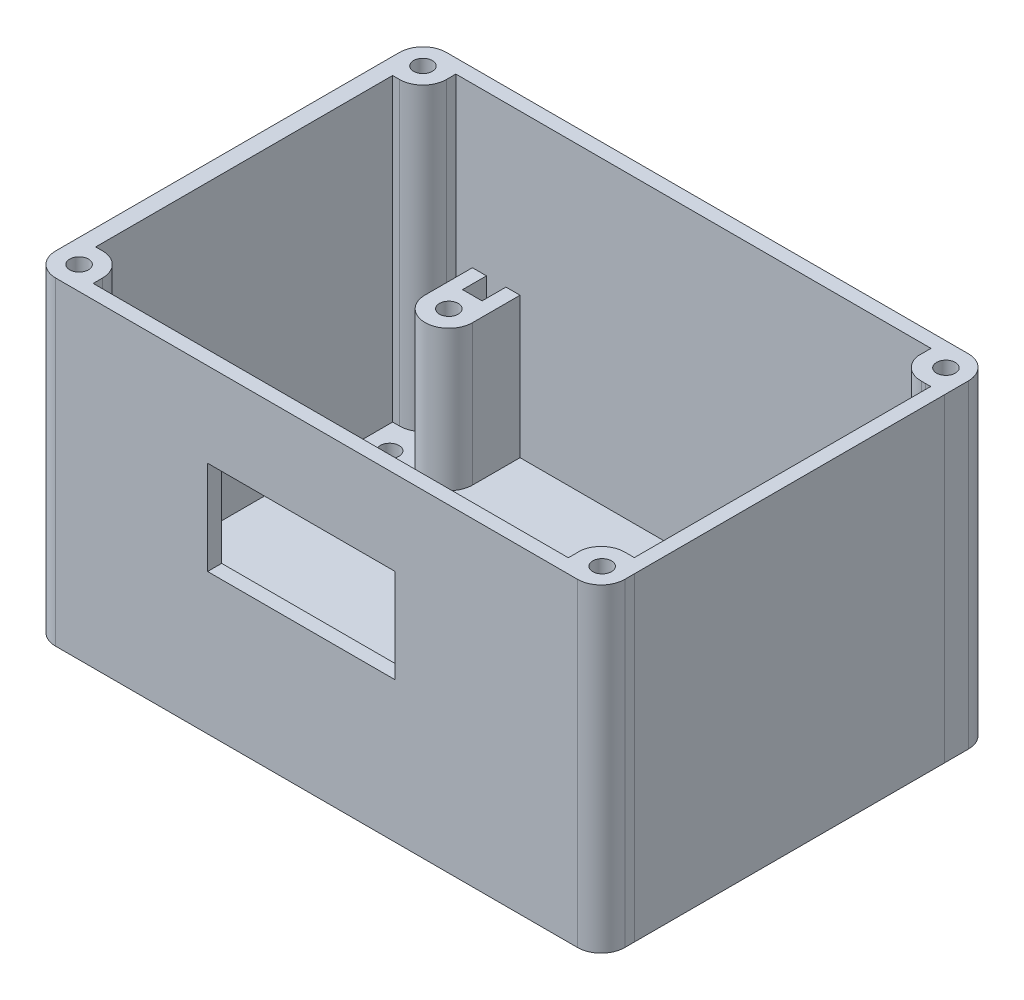
SolidWorks part; units mm, degrees
ref_plane "Front Plane" through (0, 0, 0) normal (0, 0, 1) x (1, 0, 0)
ref_plane "Top Plane" through (0, 0, 0) normal (0, 1, 0) x (1, 0, 0)
ref_plane "Right Plane" through (0, 0, 0) normal (1, 0, 0) x (0, 0, -1)
sketch "Sketch1" plane through (0, 0, 0) normal (0, 1, 0) x (1, 0, 0)
  line L0 (43.815, 0) -> (46.355, 0)
  line L1 (0, 0) -> (43.815, 0)
  line L2 (0, 0) -> (0, 28.575)
  line L3 (0, 28.575) -> (43.815, 28.575)
  line L4 (43.815, 0) -> (43.815, 28.575)
  line L5 (46.355, 0) -> (46.355, -2.54)
  line L6 (-2.54, -2.54) -> (-7.54, -2.54)
  line L7 (46.355, -2.54) -> (-2.54, -2.54)
  line L8 (46.355, -2.54) -> (46.355, 31.115)
  line L9 (46.355, 31.115) -> (-2.54, 31.115)
  line L10 (-2.54, -2.54) -> (-2.54, 31.115)
  line L11 (-7.54, -2.54) -> (-7.54, -4.54)
  line L12 (46.355, -2.54) -> (48.355, -2.54)
  line L13 (48.355, -2.54) -> (48.355, -4.54)
  line L14 (46.355, 31.115) -> (48.355, 31.115)
  line L15 (48.355, 31.115) -> (48.355, 33.115)
  line L16 (-2.54, 31.115) -> (-7.54, 31.115)
  line L17 (-7.54, 31.115) -> (-7.54, 33.115)
  line L18 (-7.54, 33.115) -> (48.355, 33.115)
  line L19 (48.355, -4.54) -> (48.355, 31.115)
  line L20 (48.355, -4.54) -> (-7.54, -4.54)
  line L21 (-7.54, 31.115) -> (-7.54, -2.54)
  line L22 (48.355, -4.54) -> (50.355, -4.54)
  line L23 (50.355, -4.54) -> (50.355, -6.54)
  line L25 (50.355, -6.54) -> (-9.305, -6.54)
  line L26 (50.355, -6.54) -> (50.355, 35.12)
  line L27 (50.355, 35.12) -> (-9.305, 35.12)
  line L28 (-9.305, -6.54) -> (-9.305, 35.12)
  line L29 (-2.54, 31.115) -> (2.54, 31.115)
  line L30 (-2.54, 31.115) -> (-2.54, 26.035)
  line L31 (-2.54, 26.035) -> (2.54, 26.035)
  line L32 (2.54, 31.115) -> (2.54, 26.035)
  line L33 (46.355, 31.115) -> (41.275, 31.115)
  line L34 (46.355, 31.115) -> (46.355, 26.035)
  line L35 (46.355, 26.035) -> (41.275, 26.035)
  line L36 (41.275, 31.115) -> (41.275, 26.035)
  line L37 (46.355, -2.54) -> (41.275, -2.54)
  line L38 (46.355, -2.54) -> (46.355, 2.54)
  line L39 (46.355, 2.54) -> (41.275, 2.54)
  line L40 (41.275, -2.54) -> (41.275, 2.54)
  line L41 (-2.54, -2.54) -> (2.54, -2.54)
  line L42 (-2.54, -2.54) -> (-2.54, 2.54)
  line L43 (-2.54, 2.54) -> (2.54, 2.54)
  line L44 (2.54, -2.54) -> (2.54, 2.54)
  circle A0 centre (0, 0) radius 1
  circle A1 centre (0, 28.575) radius 1
  circle A2 centre (43.815, 28.575) radius 1
  circle A3 centre (43.815, 0) radius 1
  dimension "D3" = 2
  dimension "D4" = 2.54
  dimension "D1" = 43.815
  dimension "D2" = 28.575
  dimension "D5" = 2.54
  dimension "D6" = 48.895
  dimension "D7" = 33.655
  dimension "D8" = 5
  dimension "D9" = 2
  dimension "D10" = 2
  dimension "D11" = 2
  dimension "D12" = 2
  dimension "D13" = 5
  dimension "D14" = 2
  dimension "D15" = 2
  dimension "D16" = 41.66
  dimension "D17" = 59.66
  dimension "D18" = 5.08
  dimension "D19" = 5.08
  dimension "D20" = 5.08
  dimension "D21" = 5.08
  dimension "D22" = 5.08
  dimension "D23" = 5.08
  dimension "D24" = 5.08
  dimension "D25" = 5.08
extrude "Boss-Extrude2" add sketch "Sketch1" along normal blind 32 contours L28 L25 L23 L20 L11 L21 L17 L18 L15 L19 L13 L26 L27 region at (49.6273, 0, 5.54)
extrude "Boss-Extrude3" add sketch "Sketch1<5>" along normal blind 15 contours A1 L3 L32 L9 L10 L31 L2 | A1 L2 L31 L32 L3 | A2 L4 L35 L8 L9 L36 L3 | A2 L3 L36 L35 L4 | L18 L17 L16 L9 L14 L15 | L20 L13 L12 L7 L6 L11 | A3 L4 L39 L40 L1 | A3 L0 L8 L39 L4 | A3 L1 L40 L7 L5 L0 | A0 L1 L44 L43 L2 | A0 L2 L43 L10 L7 L44 L1 | L42 L43 L44 L41 | A0 region at (45.2022, 0, -1.3872) region at (43.815, 0, 1.3872) region at (42.4278, 0, -1.3872) region at (20.4075, 0, 3.54) region at (2.4682, 0, 1.27) region at (1.3872, 0, -1.3872) region at (42.4278, 0, -27.1878) region at (43.8868, 0, -26.805) region at (20.4075, 0, -32.115) region at (-1.27, 0, -26.1068) region at (1.3872, 0, -27.1878)
sketch "Sketch1<5>" plane through (0, 0, 0) normal (0, 1, 0) x (1, 0, 0) same geometry as "Sketch1"
sketch "Sketch3" plane through (0, 0, 0) normal (0, -1, 0) x (-1, 0, 0)
  line L1 (9.305, -6.54) -> (-50.355, -6.54)
  line L2 (9.305, -6.54) -> (9.305, 35.12)
  line L3 (9.305, 35.12) -> (-50.355, 35.12)
  line L4 (-50.355, -6.54) -> (-50.355, 35.12)
extrude "Boss-Extrude12" add sketch "Sketch3" along normal blind 2
sketch "Sketch4" plane through (0, 15, 0) normal (0, 1, 0) x (1, 0, 0)
  line L0 (-2.54, 31.115) -> (-2.54, 33.115)
  line L1 (-7.54, 33.115) -> (48.355, 33.115) construction
  line L2 (2.54, 31.115) -> (2.54, 33.115)
  line L3 (41.275, 31.115) -> (41.275, 33.115)
  line L4 (46.355, 31.115) -> (46.355, 33.115)
  line L6 (2.54, 31.115) -> (41.275, 31.115)
  line L7 (2.54, 31.115) -> (2.54, 33.115)
  line L8 (2.54, 33.115) -> (41.275, 33.115)
  line L9 (41.275, 31.115) -> (41.275, 33.115)
  line M4 (2.54, 31.115) -> (41.275, 31.115)
  line M10 (48.355, 33.115) -> (-7.54, 33.115)
extrude "Cut-Extrude1" cut sketch "Sketch4" against normal blind 15 contours L3 L2 M4 M10 region at (21.9075, 15, -32.115)
sketch "Sketch5" plane through (0, 15, 0) normal (0, 1, 0) x (1, 0, 0)
  line L0 (-2.54, 31.115) -> (-2.5, 33.115)
  line L1 (-7.54, 33.115) -> (2.54, 33.115) construction
  line L3 (-2.54, 31.115) -> (-7.54, 31.115)
  line L4 (-2.54, 31.115) -> (-2.54, 33.115)
  line L5 (-2.54, 33.115) -> (-7.54, 33.115)
  line L6 (-7.54, 31.115) -> (-7.54, 33.115)
  line M3 (2.54, 33.115) -> (-7.54, 33.115)
  line M4 (-7.54, 33.115) -> (-7.54, 31.115)
  line M5 (-7.54, 31.115) -> (-2.54, 31.115)
extrude "Cut-Extrude2" cut sketch "Sketch5" against normal blind 15 contours L4 M5 M3 M4 region at (-5.04, 15, -32.115)
sketch "Sketch6" plane through (0, 15, 0) normal (0, 1, 0) x (1, 0, 0)
  line L0 (46.355, 31.115) -> (46.355, 33.115)
  line L1 (41.275, 33.115) -> (48.355, 33.115) construction
  line L3 (48.355, 31.115) -> (46.355, 31.115)
  line L4 (48.355, 31.115) -> (48.355, 33.115)
  line L5 (48.355, 33.115) -> (46.355, 33.115)
  line L6 (46.355, 31.115) -> (46.355, 33.115)
  line M1 (48.355, 33.115) -> (41.275, 33.115)
  line M5 (46.355, 31.115) -> (48.355, 31.115)
  line M6 (48.355, 31.115) -> (48.355, 33.115)
extrude "Cut-Extrude3" cut sketch "Sketch6" against normal blind 15 contours L0 M5 M6 M1 region at (47.355, 15, -32.115)
sketch "Sketch7" plane through (0, 15, 0) normal (0, 1, 0) x (1, 0, 0)
  line L0 (-2.54, -2.54) -> (-2.54, -4.54)
  line L1 (48.355, -4.54) -> (-7.54, -4.54) construction
  line L2 (2.54, -2.54) -> (2.54, -4.54)
  line L4 (-2.54, -2.54) -> (-7.54, -2.54)
  line L5 (-2.54, -2.54) -> (-2.54, -4.54)
  line L6 (-2.54, -4.54) -> (-7.54, -4.54)
  line L7 (-7.54, -2.54) -> (-7.54, -4.54)
  line M2 (-2.54, -2.54) -> (-7.54, -2.54)
  line M3 (-7.54, -2.54) -> (-7.54, -4.54)
  line M4 (-7.54, -4.54) -> (48.355, -4.54)
extrude "Cut-Extrude4" cut sketch "Sketch7" against normal blind 15 contours L0 M2 M3 M4 region at (-5.04, 15, 3.54)
sketch "Sketch8" plane through (0, 15, 0) normal (0, 1, 0) x (1, 0, 0)
  line L0 (46.355, -2.54) -> (46.355, -4.54)
  line L1 (48.355, -4.54) -> (-2.54, -4.54) construction
  line L2 (41.275, -2.54) -> (41.275, -4.54)
  line L3 (48.355, -2.54) -> (48.355, -4.54) construction
  line L4 (46.355, -2.54) -> (48.355, -2.54)
  line L5 (46.355, -2.54) -> (46.355, -4.54)
  line L6 (46.355, -4.54) -> (48.355, -4.54)
  line L7 (48.355, -2.54) -> (48.355, -4.54)
  line M4 (-2.54, -4.54) -> (48.355, -4.54)
  line M5 (48.355, -4.54) -> (48.355, -2.54)
  line M6 (48.355, -2.54) -> (46.355, -2.54)
extrude "Cut-Extrude5" cut sketch "Sketch8" against normal blind 15 contours L0 M6 M4 M5 region at (47.355, 15, 3.54)
sketch "Sketch9" plane through (0, 15, 0) normal (0, 1, 0) x (1, 0, 0)
  line L0 (2.54, -2.54) -> (2.54, -4.54)
  line L1 (46.355, -4.54) -> (-2.54, -4.54) construction
  line L2 (41.275, -2.54) -> (41.275, -4.54)
  line L4 (2.54, -2.54) -> (41.275, -2.54)
  line L5 (2.54, -2.54) -> (2.54, -4.54)
  line L6 (2.54, -4.54) -> (41.275, -4.54)
  line L7 (41.275, -2.54) -> (41.275, -4.54)
  line M1 (-2.54, -4.54) -> (46.355, -4.54)
  line M5 (41.275, -2.54) -> (2.54, -2.54)
extrude "Cut-Extrude6" cut sketch "Sketch9" against normal blind 15 contours L2 L0 M5 M1 region at (21.9075, 15, 3.54)
sketch "Sketch10" plane through (0, 0, 6.54) normal (0, 0, 1) x (1, 0, 0)
  line L0 (-9.305, -2) -> (9.395, -2)
  line L1 (50.355, -2) -> (-9.305, -2) construction
  line L2 (9.395, -2) -> (9.395, 13)
  line L4 (9.395, 13) -> (29.395, 13)
  line L5 (9.395, 13) -> (9.395, 23)
  line L6 (9.395, 23) -> (29.395, 23)
  line L7 (29.395, 13) -> (29.395, 23)
  dimension "D1" = 18.7
  dimension "D2" = 15
  dimension "D3" = 20
  dimension "D4" = 10
extrude "Cut-Extrude7" cut sketch "Sketch10" against normal blind 15 contours L4 L7 L6 L5 region at (19.395, 18, 6.54)
sketch "Sketch11" plane through (0, 32, 0) normal (0, 1, 0) x (1, 0, 0)
  line L1 (-9.305, 35.12) -> (-4.305, 35.12)
  line L2 (-9.305, 35.12) -> (-9.305, 30.12)
  line L3 (-9.305, 30.12) -> (-4.305, 30.12)
  line L4 (-4.305, 35.12) -> (-4.305, 30.12)
  dimension "D1" = 5
  dimension "D2" = 5
extrude "Boss-Extrude13" add sketch "Sketch11" against normal blind 32
sketch "Sketch12" plane through (0, 32, 0) normal (0, 1, 0) x (1, 0, 0)
  line L0 (-9.305, 35.12) -> (-9.305, 32.62)
  line L1 (-9.305, -6.54) -> (-9.305, 35.12) construction
  line L2 (-9.305, 32.62) -> (-6.805, 32.62)
  circle A0 centre (-6.805, 32.62) radius 1
  dimension "D3" = 2
  dimension "D1" = 2.5
  dimension "D2" = 2.5
extrude "Cut-Extrude8" cut sketch "Sketch12" against normal blind 10 contours A0 region at (-6.805, 32, -31.6483)
sketch "Sketch13" plane through (0, 32, 0) normal (0, 1, 0) x (1, 0, 0)
  line L1 (-9.305, -6.54) -> (-4.305, -6.54)
  line L2 (-9.305, -6.54) -> (-9.305, -1.54)
  line L3 (-9.305, -1.54) -> (-4.305, -1.54)
  line L4 (-4.305, -6.54) -> (-4.305, -1.54)
  dimension "D1" = 5
  dimension "D2" = 5
extrude "Boss-Extrude14" add sketch "Sketch13" against normal blind 32
sketch "Sketch14" plane through (0, 32, 0) normal (0, 1, 0) x (1, 0, 0)
  line L1 (50.355, 35.12) -> (45.355, 35.12)
  line L2 (50.355, 35.12) -> (50.355, 30.12)
  line L3 (50.355, 30.12) -> (45.355, 30.12)
  line L4 (45.355, 35.12) -> (45.355, 30.12)
  dimension "D1" = 5
  dimension "D2" = 5
extrude "Boss-Extrude15" add sketch "Sketch14" against normal blind 32
sketch "Sketch15" plane through (0, 32, 0) normal (0, 1, 0) x (1, 0, 0)
  line L1 (50.355, -6.54) -> (45.355, -6.54)
  line L2 (50.355, -6.54) -> (50.355, -1.54)
  line L3 (50.355, -1.54) -> (45.355, -1.54)
  line L4 (45.355, -6.54) -> (45.355, -1.54)
  dimension "D1" = 5
  dimension "D2" = 5
extrude "Boss-Extrude16" add sketch "Sketch15" against normal blind 32
sketch "Sketch16" plane through (0, 32, 0) normal (0, 1, 0) x (1, 0, 0)
  line L0 (50.355, 35.12) -> (47.855, 35.12)
  line L1 (50.355, 35.12) -> (-9.305, 35.12) construction
  line L2 (47.855, 35.12) -> (47.855, 32.62)
  circle A0 centre (47.855, 32.62) radius 1.012
  dimension "D1" = 2.5
  dimension "D2" = 2.5
extrude "Cut-Extrude9" cut sketch "Sketch16" against normal blind 10 contours A0 region at (47.1596, 32, -31.9246)
sketch "Sketch17" plane through (0, 32, 0) normal (0, 1, 0) x (1, 0, 0)
  line L0 (50.355, -6.54) -> (47.855, -6.54)
  line L1 (50.355, -6.54) -> (-9.305, -6.54) construction
  line L2 (50.355, -6.54) -> (50.355, -4.1861)
  line L3 (50.355, 35.12) -> (50.355, -6.54) construction
  line L4 (47.855, -6.54) -> (47.855, -4.04)
  circle A0 centre (47.855, -4.04) radius 1.012
  dimension "D1" = 2.5
  dimension "D2" = 2.5
extrude "Cut-Extrude10" cut sketch "Sketch17" against normal blind 10 contours A0 region at (48.5504, 32, 4.7354)
sketch "Sketch18" plane through (0, 32, 0) normal (0, 1, 0) x (1, 0, 0)
  line L0 (-9.305, -6.54) -> (-9.305, -4.04)
  line L1 (-9.305, -6.54) -> (-9.305, 35.12) construction
  line L2 (-9.305, -4.04) -> (-6.805, -4.04)
  circle A0 centre (-6.805, -4.04) radius 1
  dimension "D1" = 2.5
  dimension "D2" = 2.5
extrude "Cut-Extrude11" cut sketch "Sketch18" against normal blind 10 contours A0 region at (-6.805, 32, 5.0117)
sketch "Sketch19" plane through (0, 32, 0) normal (0, 1, 0) x (1, 0, 0)
  line L0 (45.355, 33.115) -> (48.355, 30.12)
  line L1 (45.355, 33.115) -> (45.355, 30.12)
  line L2 (45.355, 30.12) -> (48.355, 30.12)
extrude "Cut-Extrude12" cut sketch "Sketch19" against normal blind 17
sketch "Sketch20" plane through (0, 32, 0) normal (0, 1, 0) x (1, 0, 0)
  line L0 (45.355, -4.54) -> (48.355, -1.54)
  line L1 (48.355, -1.54) -> (48.355, 30.12) construction
  line L2 (48.355, -1.54) -> (45.355, -1.54)
  line L3 (45.355, -1.54) -> (45.355, -4.54)
extrude "Cut-Extrude13" cut sketch "Sketch20" against normal blind 17
sketch "Sketch23" plane through (0, 32, 0) normal (0, 1, 0) x (1, 0, 0)
  line L0 (50.355, 35.12) -> (47.855, 35.12)
  line L1 (50.355, 35.12) -> (-9.305, 35.12) construction
  line L2 (47.855, 35.12) -> (47.855, 32.62)
  circle A0 centre (47.855, 32.62) radius 2.5
  line M18 (50.355, -6.54) -> (50.355, 35.12)
  line M19 (50.355, 35.12) -> (-9.305, 35.12)
  dimension "D3" = 5
  dimension "D1" = 2.5
  dimension "D2" = 2.5
extrude "Cut-Extrude14" cut sketch "Sketch23" against normal blind 47 contours A0 M18 M19 region at (49.7966, 32, -34.5616)
sketch "Sketch24" plane through (0, 32, 0) normal (0, 1, 0) x (1, 0, 0)
  line L0 (50.355, -6.54) -> (47.855, -6.54)
  line L1 (50.355, -6.54) -> (-9.305, -6.54) construction
  line L2 (47.855, -6.54) -> (47.855, -4.04)
  circle A0 centre (47.855, -4.04) radius 2.5
  line M17 (50.355, -6.54) -> (50.355, 32.62)
  line M21 (-9.305, -6.54) -> (50.355, -6.54)
  dimension "D3" = 5
  dimension "D1" = 2.5
  dimension "D2" = 2.5
extrude "Cut-Extrude15" cut sketch "Sketch24" against normal blind 47 contours A0 M21 M17 region at (49.7966, 32, 5.9816)
sketch "Sketch25" plane through (0, 32, 0) normal (0, 1, 0) x (1, 0, 0)
  line L0 (-9.305, -6.54) -> (-6.805, -6.54)
  line L1 (47.855, -6.54) -> (-9.305, -6.54) construction
  line L2 (-6.805, -6.54) -> (-6.805, -4.04)
  circle A0 centre (-6.805, -4.04) radius 2.5
  line M16 (-9.305, -6.54) -> (47.855, -6.54)
  line M21 (-9.305, 35.12) -> (-9.305, -6.54)
  dimension "D1" = 2.5
extrude "Cut-Extrude16" cut sketch "Sketch25" against normal blind 47 contours A0 M21 M16 region at (-8.7466, 32, 5.9816)
sketch "Sketch26" plane through (0, 32, 0) normal (0, 1, 0) x (1, 0, 0)
  line L0 (-9.305, 35.12) -> (-6.805, 35.12)
  line L1 (47.855, 35.12) -> (-9.305, 35.12) construction
  line L2 (-6.805, 35.12) -> (-6.805, 32.62)
  circle A0 centre (-6.805, 32.62) radius 2.5
  line M17 (-9.305, 35.12) -> (-9.305, -4.04)
  line M23 (47.855, 35.12) -> (-9.305, 35.12)
  dimension "D1" = 2.5
  dimension "D2" = 2.5
extrude "Cut-Extrude17" cut sketch "Sketch26" against normal blind 47 contours A0 M23 M17 region at (-8.7466, 32, -34.5616)
sketch "Sketch27" plane through (0, 32, 0) normal (0, 1, 0) x (1, 0, 0)
  line L0 (45.355, -4.54) -> (45.355, -1.54)
  line L1 (48.355, -1.54) -> (45.355, -1.54)
  line L2 (45.355, -1.54) -> (47.855, -1.54)
  line L3 (47.855, -1.54) -> (47.855, -4.04)
  circle A0 centre (47.855, -4.04) radius 2.5
  line M1 (48.355, -1.54) -> (45.355, -4.54)
  dimension "D1" = 2.5
  dimension "D2" = 2.5
extrude "Boss-Extrude18" add sketch "Sketch27" against normal blind 27 contours L3 A0 M1 | A0 L3 M1 region at (46.4843, 32, 2.7656) region at (48.0097, 32, 1.7162)
sketch "Sketch28" plane through (0, 32, 0) normal (0, 1, 0) x (1, 0, 0)
  line L0 (-4.305, -1.54) -> (-6.805, -1.54)
  line L1 (-4.305, -1.54) -> (-7.54, -1.54) construction
  line L2 (-6.805, -1.54) -> (-6.805, -4.04)
  circle A0 centre (-6.805, -4.04) radius 2.5
  line M4 (-4.305, -4.54) -> (-4.305, -1.54)
  line M5 (-4.305, -1.54) -> (-7.54, -1.54)
  dimension "D1" = 2.5
extrude "Cut-Extrude19" cut sketch "Sketch28" against normal blind 32 contours A0 M4 M5 region at (-4.8634, 32, 2.0984)
sketch "Sketch29" plane through (0, 32, 0) normal (0, 1, 0) x (1, 0, 0)
  line L0 (-4.305, 30.12) -> (-6.805, 30.12)
  line L1 (-4.305, 30.12) -> (-7.54, 30.12) construction
  line L2 (-6.805, 30.12) -> (-6.805, 32.62)
  circle A0 centre (-6.805, 32.62) radius 2.5
  line M19 (-7.54, 30.12) -> (-4.305, 30.12)
  line M20 (-4.305, 30.12) -> (-4.305, 33.115)
  dimension "D1" = 2.5
  dimension "D2" = 2.5
extrude "Cut-Extrude20" cut sketch "Sketch29" against normal blind 32 contours A0 M19 M20 region at (-4.8634, 32, -30.6784)
sketch "Sketch40" plane through (0, 15, 0) normal (0, 1, 0) x (1, 0, 0)
  line L0 (46.355, -1.54) -> (46.355, -2.0674)
  line L1 (46.355, -2.0674) -> (48.355, -1.54)
  line L2 (48.355, -1.54) -> (46.355, -1.54)
extrude "Cut-Extrude28" cut sketch "Sketch40" against normal blind 15
sketch "Sketch41" plane through (0, 32, 0) normal (0, 1, 0) x (1, 0, 0)
  line L0 (45.355, -4.54) -> (45.355, 0)
  line L1 (45.355, 0) -> (50.355, 0)
  line L2 (50.355, 32.62) -> (50.355, -4.04) construction
  line L3 (48.355, -1.54) -> (45.355, -4.54)
  line L4 (48.355, -1.54) -> (48.355, 0)
  line L5 (48.355, -1.54) -> (48.355, 30.12) construction
  line M21 (48.355, 30.12) -> (48.355, -1.54)
  line M22 (48.355, -1.54) -> (48.3127, -1.5823)
  arc M23 (48.3127, -1.5823) -> (45.3973, -4.4977) centre (47.855, -4.04) ccw
extrude "Cut-Extrude29" cut sketch "Sketch41" against normal blind 17 contours L1 L0 M23 M22 M21 | L3 M23 region at (46.6451, 32, 1.0695) region at (46.5413, 32, 2.7263)
sketch "Sketch42" plane through (0, 15, 0) normal (0, 1, 0) x (1, 0, 0)
  line L0 (48.355, -1.54) -> (46.355, -1.54)
  line L1 (46.355, 2.54) -> (46.355, -2.0674) construction
  line L2 (46.355, -1.54) -> (46.355, -2.0674)
  line L3 (46.355, -2.0674) -> (48.355, -1.54)
extrude "Boss-Extrude24" add sketch "Sketch42" against normal blind 15
sketch "Sketch43" plane through (0, 15, 0) normal (0, 1, 0) x (1, 0, 0)
  line L0 (48.355, 30.12) -> (46.355, 30.12)
  line L1 (46.355, 30.12) -> (46.355, 32.1167)
  line L2 (48.355, 30.12) -> (45.355, 33.115) construction
  line L3 (46.355, 32.1167) -> (48.355, 30.12)
extrude "Boss-Extrude25" add sketch "Sketch43" along normal blind 17
sketch "Sketch44" plane through (0, 32, 0) normal (0, 1, 0) x (1, 0, 0)
  line L0 (46.355, 32.1167) -> (43.855, 32.1167)
  line L1 (43.855, 32.1167) -> (43.855, 33.115)
  line L2 (-4.305, 33.115) -> (45.355, 33.115) construction
  line L3 (43.855, 33.115) -> (45.355, 33.115)
  line L4 (45.355, 33.115) -> (46.355, 32.1167)
  dimension "D1" = 2.5
extrude "Boss-Extrude26" add sketch "Sketch44" against normal blind 17
sketch "Sketch45" plane through (0, 32, 0) normal (0, 1, 0) x (1, 0, 0)
  line L0 (45.355, -4.54) -> (45.355, -6.54)
  line L1 (47.855, -6.54) -> (-6.805, -6.54) construction
  line L2 (48.355, -1.54) -> (50.355, -1.54)
  line L3 (50.355, 32.62) -> (50.355, -4.04) construction
  line L4 (50.355, -1.54) -> (52.355, -1.54)
  line L5 (52.355, -1.54) -> (52.355, -6.54)
  line L6 (45.355, -6.54) -> (52.355, -6.54)
  line L7 (52.355, -1.54) -> (52.355, 37.12)
  line L8 (43.855, 33.115) -> (43.855, 35.12)
  line L9 (47.855, 35.12) -> (-6.805, 35.12) construction
  line L10 (43.855, 35.12) -> (43.855, 37.12)
  line L11 (43.855, 37.12) -> (52.355, 37.12)
  line L12 (46.355, 30.12) -> (46.355, -6.54)
  line L13 (46.355, 30.12) -> (46.355, 37.12)
  circle M3 centre (47.855, -4.04) radius 1.012
  circle M4 centre (47.855, 32.62) radius 1.012
  line M6 (47.855, 35.12) -> (-6.805, 35.12)
  arc M11 (47.855, -6.54) -> (50.355, -4.04) centre (47.855, -4.04) ccw
  line M12 (50.355, -4.04) -> (50.355, 32.62)
  arc M13 (50.355, 32.62) -> (47.855, 35.12) centre (47.855, 32.62) ccw
  line M14 (48.355, 30.12) -> (48.355, -1.54)
  line M15 (48.355, -1.54) -> (45.355, -4.54)
  line M27 (46.355, 32.1167) -> (46.355, 30.12)
  line M28 (46.355, 30.12) -> (48.355, 30.12)
  dimension "D1" = 2
extrude "Boss-Extrude27" add sketch "Sketch45" against normal blind 34 contours L13 L4 L7 L11 M6 M13 M12 | L6 L5 L4 M11 M12 | L12 L6 L2 M15 M11 M12 M3 | M3 | M4 | L13 L2 M27 M28 M14 M12 M13 M6 M4 | L12 M28 M15 M14 region at (47.4003, 32, 2.5853) region at (47.3448, 32, -13.7849) region at (49.1548, 32, -17.8506) region at (51.1707, 32, 4.2696) region at (51.0539, 32, -19.7417) region at (47.855, 32, 4.04) region at (47.855, 32, -32.62)
sketch "Sketch46" plane through (0, 32, 0) normal (0, 1, 0) x (1, 0, 0)
  line L1 (46.355, 35.12) -> (52.355, 35.12)
  line L2 (46.355, 35.12) -> (46.355, 37.12)
  line L3 (46.355, 37.12) -> (52.355, 37.12)
  line L4 (52.355, 35.12) -> (52.355, 37.12)
extrude "Cut-Extrude30" cut sketch "Sketch46" against normal blind 34
sketch "Sketch47" plane through (0, 32, 0) normal (0, 1, 0) x (1, 0, 0)
  line L0 (46.355, 32.1167) -> (46.355, 33.115)
  line L1 (43.855, 33.115) -> (46.355, 33.115)
  line L2 (46.355, 32.1167) -> (43.855, 32.1167)
  line L3 (43.855, 32.1167) -> (43.855, 33.115)
extrude "Cut-Extrude31" cut sketch "Sketch47" against normal blind 17
sketch "Sketch48" plane through (0, 32, 0) normal (0, 1, 0) x (1, 0, 0)
  line L0 (52.355, 35.12) -> (48.835, 35.12)
  line L1 (52.355, 35.12) -> (-6.805, 35.12) construction
  line L2 (48.835, 35.12) -> (48.835, 32.604)
  line L3 (48.835, 32.604) -> (46.319, 32.604)
  line L4 (46.355, 33.115) -> (46.319, 33.115)
  line L5 (46.319, 32.604) -> (46.319, 33.115)
  line L6 (52.355, -6.54) -> (48.839, -6.54)
  line L7 (52.355, -6.54) -> (-6.805, -6.54) construction
  line L8 (48.839, -6.54) -> (48.839, -4.024)
  line L9 (48.835, 30.088) -> (52.355, 30.088)
  line L10 (52.355, -6.54) -> (52.355, 35.12) construction
  line L11 (52.355, 30.088) -> (50.355, 30.088)
  line L12 (48.839, -3.008) -> (52.355, -3.008)
  line L13 (52.355, -3.008) -> (50.355, -3.008)
  line L14 (50.355, -3.008) -> (50.355, 30.088)
  line L15 (48.839, -1.508) -> (52.355, -1.508)
  line L16 (52.355, -1.508) -> (50.355, -1.508)
  line L17 (46.355, -3.54) -> (46.355, -6.54)
  line L18 (52.355, 30.088) -> (50.355, 30.088)
  line L19 (52.355, 30.088) -> (52.355, -1.508)
  line L20 (52.355, -1.508) -> (50.355, -1.508)
  line L21 (50.355, 30.088) -> (50.355, -1.508)
  line L22 (46.355, -6.54) -> (46.355, -4.54)
  line L23 (46.355, -4.54) -> (46.3765, -4.54)
  circle A0 centre (48.835, 32.604) radius 1.016
  circle A1 centre (48.839, -4.024) radius 1.016
  circle A3 centre (48.835, 32.604) radius 2.516
  circle A4 centre (48.839, -4.024) radius 2.516
  line M4 (46.355, 33.115) -> (46.355, -3.54)
  line M14 (52.355, -6.54) -> (52.355, 35.12)
  line M15 (52.355, 35.12) -> (-6.805, 35.12)
  line M19 (-6.805, -6.54) -> (52.355, -6.54)
  dimension "D3" = 2.516
  dimension "D6" = 2
  dimension "D8" = 2
  dimension "D1" = 3.52
  dimension "D2" = 2.516
  dimension "D4" = 3.516
  dimension "D5" = 2.516
  dimension "D7" = 2
extrude "Cut-Extrude33" cut sketch "Sketch48" against normal blind 37 contours A4 M19 M14 | A3 M14 M15 region at (51.4809, 32, -32.604) region at (51.5561, 32, 5.0819)
extrude "Cut-Extrude34" cut sketch "Sketch48<5>" against normal blind 32 contours A4 L15 L14 L9 A3 L5 L4 L17 L23 M4 region at (48.3264, 32, -14.2889)
sketch "Sketch48<5>" plane through (0, 32, 0) normal (0, 1, 0) x (1, 0, 0) same geometry as "Sketch48"
sketch "Sketch51" plane through (0, 32, 0) normal (0, 1, 0) x (1, 0, 0)
  line L2 (46.355, -3.54) -> (45.355, -4.54)
sketch "Sketch52" plane through (0, 32, 0) normal (0, 1, 0) x (1, 0, 0)
  line L0 (51.355, -4.024) -> (51.351, 32.604)
  line L1 (51.351, 32.604) -> (49.351, 32.604)
  line L2 (49.351, 32.604) -> (49.0223, -4.024)
  line L3 (49.0223, -4.024) -> (51.355, -4.024)
  arc A0 (48.839, -6.54) -> (51.1407, -3.008) centre (48.839, -4.024) ccw construction
  arc A1 (46.355, 32.1799) -> (48.835, 35.12) centre (48.835, 32.604) ccw construction
  dimension "D1" = 2
extrude "Boss-Extrude28" add sketch "Sketch52" against normal blind 34
sketch "Sketch53" plane through (0, 32, 0) normal (0, 1, 0) x (1, 0, 0)
  line L0 (51.3513, 30.088) -> (51.3549, -3.008)
  line L2 (52.355, 30.088) -> (51.3549, 30.088)
  line L3 (52.355, 30.088) -> (52.355, -3.008)
  line L4 (52.355, -3.008) -> (51.3549, -3.008)
  line L5 (51.3549, 30.088) -> (51.3549, -3.008)
  line M4 (51.3549, -3.008) -> (52.355, -3.008)
  line M5 (52.355, -3.008) -> (52.355, 30.088)
  line M6 (52.355, 30.088) -> (51.3513, 30.088)
extrude "Cut-Extrude35" cut sketch "Sketch53" against normal blind 34 contours L5 M6 M4 M5 region at (51.8549, 32, -13.54)
sketch "Sketch54" plane through (0, 32, 0) normal (0, 1, 0) x (1, 0, 0)
  line L0 (49.0449, -1.508) -> (48.839, -6.54)
  line L1 (48.839, -6.54) -> (48.942, -4.024)
  arc A0 (48.839, -6.54) -> (51.355, -4.0237) centre (48.839, -4.024) ccw construction
  circle A1 centre (48.942, -4.024) radius 1
  dimension "D1" = 2.516
extrude "Cut-Extrude36" cut sketch "Sketch54" against normal blind 10 contours L0 A1 | L0 A1 region at (49.366, 32, 4.0414) region at (48.5179, 32, 4.0066)
sketch "Sketch55" plane through (0, 32, 0) normal (0, 1, 0) x (1, 0, 0)
  line L0 (49.3289, 30.1369) -> (49.3289, 35.0711)
  line L1 (49.3289, 35.0711) -> (49.3289, 32.5551)
  arc A0 (51.351, 32.604) -> (48.835, 35.12) centre (48.835, 32.604) ccw construction
  circle A1 centre (49.3289, 32.5551) radius 1.016
  dimension "D1" = 2.516
extrude "Cut-Extrude37" cut sketch "Sketch55" against normal blind 10 contours L0 A1 | L0 A1 region at (48.8977, 32, -32.5551) region at (49.7601, 32, -32.5551)
sketch "Sketch56" plane through (0, 32, 0) normal (0, 1, 0) x (1, 0, 0)
  line L0 (45.355, -4.54) -> (46.7341, -4.54)
  line L1 (46.355, -3.624) -> (46.355, -4.54)
  line L2 (46.355, -3.624) -> (46.355, -3.54)
  line L3 (46.355, -3.54) -> (45.355, -4.54)
  line M18 (46.355, -3.624) -> (46.355, -3.54)
  line M19 (46.355, -3.54) -> (45.355, -4.54)
extrude "Cut-Extrude38" cut sketch "Sketch56" against normal blind 17 contours L1 L0 M18 M19 region at (46.0217, 32, 4.2067)
sketch "Sketch60" plane through (51.3549, 0, 0) normal (1, 0, 0) x (0, 0, -1)
  line L0 (-3.008, 32) -> (13.54, 32)
  line L1 (30.088, 32) -> (-3.008, 32) construction
  line L2 (13.54, 32) -> (13.54, 22)
  line L3 (13.54, 22) -> (19.54, 22)
  line L4 (13.54, 22) -> (7.54, 22)
  line L5 (19.54, 22) -> (19.54, 23)
  line L6 (19.54, 22) -> (19.54, 21)
  line L7 (7.54, 22) -> (7.54, 23)
  line L8 (7.54, 22) -> (7.54, 21)
  line L9 (7.54, 23) -> (19.54, 23)
  line L10 (7.54, 21) -> (19.54, 21)
  line L11 (13.54, 22) -> (18.89, 22)
  line L12 (18.89, 22) -> (18.89, 23.8166)
  line L13 (18.89, 22) -> (18.89, 20.1834)
  line L14 (13.54, 22) -> (8.19, 22)
  line L15 (8.19, 22) -> (8.19, 23.8166)
  circle A0 centre (13.54, 22) radius 5.65
  dimension "D2" = 6
  dimension "D8" = 5.35
  dimension "D1" = 10
  dimension "D3" = 6
  dimension "D4" = 1
  dimension "D5" = 1
  dimension "D6" = 1
  dimension "D7" = 1
  dimension "D9" = 5.35
sketch "Sketch61" plane through (0, 15, 0) normal (0, 1, 0) x (1, 0, 0)
  line L0 (0, 27.575) -> (0, 26.035)
  line L1 (-2.54, 26.035) -> (2.54, 26.035) construction
  line L2 (1, 28.575) -> (2.54, 28.575)
  line L3 (2.54, 33.115) -> (2.54, 26.035) construction
  line L4 (-1, 28.575) -> (-2.54, 28.575)
  line L5 (-2.54, 26.035) -> (-2.54, 33.115) construction
  line L6 (-2.54, 31.075) -> (-1.04, 31.075)
  line L8 (0, 29.575) -> (0, 31.075)
  line L9 (0, 31.075) -> (2.54, 31.075)
  line L10 (0, 31.075) -> (-2.54, 31.075)
  line L11 (-2.54, 31.075) -> (2.54, 31.075)
  line L12 (-2.54, 31.075) -> (-2.54, 33.115)
  line L13 (-2.54, 33.115) -> (2.54, 33.115)
  line L14 (2.54, 31.075) -> (2.54, 33.115)
  line L15 (2.54, 31.075) -> (1.04, 31.075)
  line L16 (-1.04, 31.075) -> (-1.04, 33.115)
  line L17 (-1.04, 33.115) -> (1.04, 33.115)
  line L18 (1.04, 33.115) -> (1.04, 31.075)
  circle A0 centre (0, 28.575) radius 1 construction
  circle A1 centre (0, 28.575) radius 1 construction
  dimension "D1" = 1.5
  dimension "D2" = 1.5
  dimension "D3" = 1.5
extrude "Cut-Extrude41" cut sketch "Sketch61" against normal blind 15 contours L18 L13 L16 L10 L9 region at (0, 15, -32.095)
sketch "Sketch62" plane through (0, 15, 0) normal (0, 1, 0) x (1, 0, 0)
  line L0 (43.815, 29.575) -> (43.815, 31.075)
  line L1 (43.815, 31.075) -> (41.275, 31.075)
  line L2 (41.275, 33.115) -> (41.275, 26.035) construction
  line L3 (43.815, 31.075) -> (46.355, 31.075)
  line L4 (46.355, 32.1799) -> (46.355, 26.035) construction
  line L5 (41.275, 31.075) -> (42.775, 31.075)
  line L6 (46.355, 31.075) -> (44.855, 31.075)
  line L7 (42.775, 31.075) -> (42.775, 33.115)
  line L8 (41.275, 33.115) -> (46.355, 33.115) construction
  line L9 (42.775, 33.115) -> (44.855, 33.115)
  line L10 (44.855, 33.115) -> (44.855, 31.075)
  circle A0 centre (43.815, 28.575) radius 1 construction
  circle A1 centre (43.815, 28.575) radius 1 construction
  line M4 (46.355, 33.115) -> (41.275, 33.115)
  dimension "D1" = 1.5
  dimension "D2" = 1.5
  dimension "D3" = 1.5
extrude "Cut-Extrude42" cut sketch "Sketch62" against normal blind 15 contours L10 L7 L1 L3 M4 region at (43.815, 15, -32.095)
sketch "Sketch63" plane through (0, 15, 0) normal (0, 1, 0) x (1, 0, 0)
  line L0 (0, -1) -> (0, -2.5)
  line L1 (0, -2.5) -> (2.54, -2.5)
  line L2 (2.54, -4.54) -> (2.54, 2.54) construction
  line L3 (0, -2.5) -> (-2.54, -2.5)
  line L4 (-2.54, -4.54) -> (-2.54, 2.54) construction
  line L5 (2.54, -2.5) -> (1.04, -2.5)
  line L6 (-2.54, -2.5) -> (-1.04, -2.5)
  line L7 (-1.04, -2.5) -> (-1.04, -4.54)
  line L8 (2.54, -4.54) -> (-2.54, -4.54) construction
  line L9 (1.04, -2.5) -> (1.04, -4.54)
  circle A0 centre (0, 0) radius 1 construction
  line M2 (-2.54, -4.54) -> (2.54, -4.54)
  dimension "D1" = 1.5
  dimension "D2" = 1.5
  dimension "D3" = 1.5
extrude "Cut-Extrude43" cut sketch "Sketch63" against normal blind 15 contours L9 L1 L3 L7 M2 region at (0, 15, 3.52)
sketch "Sketch64" plane through (0, 15, 0) normal (0, 1, 0) x (1, 0, 0)
  line L0 (43.815, -1) -> (43.815, -2.5)
  line L1 (43.815, -2.5) -> (46.355, -2.5)
  line L2 (46.355, 2.54) -> (46.355, -3.624) construction
  line L3 (43.815, -2.5) -> (41.275, -2.5)
  line L4 (41.275, -4.54) -> (41.275, 2.54) construction
  line L5 (41.275, -2.5) -> (42.775, -2.5)
  line L6 (46.355, -2.5) -> (44.855, -2.5)
  line L7 (42.775, -2.5) -> (42.775, -4.54)
  line L8 (46.355, -4.54) -> (41.275, -4.54) construction
  line L9 (44.855, -2.5) -> (44.855, -4.54)
  line L10 (42.775, -4.54) -> (44.855, -4.54)
  circle A0 centre (43.815, 0) radius 1 construction
  line M3 (41.275, -4.54) -> (46.355, -4.54)
  dimension "D1" = 1.5
  dimension "D2" = 1.5
  dimension "D3" = 1.5
extrude "Cut-Extrude44" cut sketch "Sketch64" against normal blind 15 contours L9 L1 L3 L7 M3 region at (43.815, 15, 3.52)
sketch "Sketch65" plane through (0, 32, 0) normal (0, 1, 0) x (1, 0, 0)
  line L0 (49.942, -4.024) -> (51.355, -4.0237)
  circle A0 centre (48.942, -4.024) radius 1 construction
  circle A1 centre (49.3289, 32.5551) radius 1.016
  circle M1 centre (49.3289, 32.5551) radius 1.016
extrude "Boss-Extrude29" add sketch "Sketch65" against normal blind 15 contours M1 region at (49.3289, 32, -32.5551)
sketch "Sketch66" plane through (0, 32, 0) normal (0, 1, 0) x (1, 0, 0)
  line L0 (48.839, -6.54) -> (49.0449, -1.508)
  line L1 (-6.805, 31.62) -> (-6.805, -4.04)
  circle A0 centre (-6.805, 32.62) radius 1 construction
  circle A1 centre (-6.805, 32.62) radius 1 construction
  circle A4 centre (48.942, 32.632) radius 1
extrude "Cut-Extrude45" cut sketch "Sketch66" against normal blind 10 contours A4 region at (48.942, 32, -32.632)
sketch "Sketch67" plane through (0, 15, 0) normal (0, 1, 0) x (1, 0, 0)
  line L0 (41.275, 28.575) -> (41.275, 26.035)
  line L1 (41.275, 26.035) -> (43.815, 26.035)
  line L2 (43.815, 26.035) -> (46.355, 26.035)
  line L3 (46.355, 26.035) -> (41.275, 26.035) construction
  line L4 (46.355, 26.035) -> (46.355, 28.575)
  circle A0 centre (43.815, 28.575) radius 2.54
  line M8 (41.275, 33.115) -> (41.275, 26.035)
  line M9 (41.275, 26.035) -> (46.355, 26.035)
  line M10 (46.355, 26.035) -> (46.355, 32.1799)
extrude "Cut-Extrude47" cut sketch "Sketch67" against normal blind 15 contours A0 M8 M9 | A0 M9 M10 region at (41.8424, 15, -26.6024) region at (45.7876, 15, -26.6024)
sketch "Sketch69" plane through (0, 15, 0) normal (0, 1, 0) x (1, 0, 0)
  line L0 (-2.54, 28.575) -> (-2.54, 26.035)
  line L1 (-2.54, 26.035) -> (2.54, 26.035) construction
  line L2 (-2.54, 26.035) -> (2.54, 26.035) construction
  line L3 (-2.54, 26.035) -> (0, 26.035)
  line L4 (0, 26.035) -> (2.54, 26.035)
  line L5 (2.54, 26.035) -> (2.54, 28.575)
  circle A0 centre (0, 28.575) radius 2.54
  line M7 (-2.54, 33.115) -> (-2.54, 26.035)
  line M8 (-2.54, 26.035) -> (2.54, 26.035)
  line M9 (2.54, 26.035) -> (2.54, 33.115)
extrude "Cut-Extrude48" cut sketch "Sketch69" against normal blind 15 contours A0 M7 M8 | A0 M8 M9 region at (-1.9726, 15, -26.6024) region at (1.9726, 15, -26.6024)
sketch "Sketch70" plane through (0, 15, 0) normal (0, 1, 0) x (1, 0, 0)
  line L0 (0, 2.54) -> (2.54, 2.54)
  line L1 (2.54, 2.54) -> (2.54, 0)
  line L2 (0, 2.54) -> (-2.54, 2.54)
  line L3 (-2.54, 2.54) -> (-2.54, 0)
  circle A0 centre (0, 0) radius 2.54
  line M5 (2.54, -4.54) -> (2.54, 2.54)
  line M6 (2.54, 2.54) -> (-2.54, 2.54)
  line M7 (-2.54, 2.54) -> (-2.54, -4.54)
extrude "Cut-Extrude49" cut sketch "Sketch70" against normal blind 15 contours A0 M5 M6 | A0 M6 M7 region at (-1.9726, 15, -1.9726) region at (1.9726, 15, -1.9726)
sketch "Sketch71" plane through (0, 15, 0) normal (0, 1, 0) x (1, 0, 0)
  line L0 (46.355, 0) -> (46.355, 2.54)
  line L1 (46.355, 2.54) -> (43.815, 2.54)
  line L2 (43.815, 2.54) -> (41.275, 2.54)
  line L3 (41.275, 2.54) -> (41.275, 0)
  circle A0 centre (43.815, 0) radius 2.54
  line M6 (46.355, -3.624) -> (46.355, 2.54)
  line M7 (46.355, 2.54) -> (41.275, 2.54)
  line M8 (41.275, 2.54) -> (41.275, -4.54)
extrude "Cut-Extrude50" cut sketch "Sketch71" against normal blind 15 contours A0 M6 M7 | A0 M7 M8 region at (45.7876, 15, -1.9726) region at (41.8424, 15, -1.9726)
sketch "Sketch72" plane through (0, 0, 0) normal (0, 1, 0) x (1, 0, 0)
  line L0 (0, 26.035) -> (43.815, 26.035)
  line L1 (43.815, 26.035) -> (43.815, 2.54)
  line L2 (43.815, 2.54) -> (0, 2.54)
  line L3 (0, 2.54) -> (0, 26.035)
  line L4 (43.815, 26.035) -> (49.2921, 26.035)
  line L5 (49.0449, -1.508) -> (49.3284, 30.088) construction
  line L6 (49.2921, 26.035) -> (46.355, 28.575)
  line L7 (0, 26.035) -> (-7.54, 26.035)
  line L8 (-7.54, 30.12) -> (-7.54, -1.54) construction
  line L9 (-7.54, 26.035) -> (-2.54, 28.575)
  line L10 (43.815, 2.54) -> (49.0812, 2.54)
  line L11 (49.0812, 2.54) -> (46.355, 0)
  line L12 (0, 2.54) -> (-7.54, 2.54)
  line L13 (-7.54, 2.54) -> (-2.54, 0)
  arc A0 (-2.54, 28.575) -> (2.54, 28.575) centre (0, 28.575) ccw construction
  arc A1 (41.275, 28.575) -> (46.355, 28.575) centre (43.815, 28.575) ccw construction
  arc A2 (46.355, 0) -> (41.275, 0) centre (43.815, 0) ccw construction
  arc A3 (2.54, 0) -> (-2.54, 0) centre (0, 0) ccw construction
  circle A4 centre (47.8235, 27.305) radius 1
  circle A5 centre (-5.04, 27.305) radius 1
  circle A6 centre (47.7181, 1.27) radius 1
  circle A7 centre (-5.04, 1.27) radius 1
extrude "Cut-Extrude51" cut sketch "Sketch72" against normal blind 10 contours L13 A7 | L13 A7 | L11 A6 | L11 A6 | L6 A4 | L6 A4 | L9 A5 | L9 A5 region at (47.5459, 0, -26.984) region at (48.1011, 0, -27.626) region at (48.0074, 0, -0.9595) region at (47.4288, 0, -1.5805) region at (-4.8478, 0, -1.6484) region at (-5.2322, 0, -0.8916) region at (-5.2322, 0, -27.6834) region at (-4.8478, 0, -26.9266)
sketch "Sketch73" plane through (0, 32, 0) normal (0, 1, 0) x (1, 0, 0)
  line L0 (46.355, 33.115) -> (46.355, 35.12)
  line L1 (48.835, 35.12) -> (-6.805, 35.12) construction
  line L2 (-4.305, 33.115) -> (-4.305, 35.12)
  line L3 (-4.305, 33.115) -> (-4.305, 33.625)
  line L5 (-4.305, 33.625) -> (46.355, 33.625)
  line L6 (-4.305, 33.625) -> (-4.305, 33.115)
  line L7 (-4.305, 33.115) -> (46.355, 33.115)
  line L8 (46.355, 33.625) -> (46.355, 33.115)
  line M26 (-4.305, 33.115) -> (46.355, 33.115)
  dimension "D1" = 0.51
extrude "Cut-Extrude52" cut sketch "Sketch73" against normal blind 32 contours L5 L2 L0 M26 region at (21.025, 32, -33.37)
sketch "Sketch74" plane through (0, 0, 0) normal (0, 1, 0) x (1, 0, 0)
  line L0 (41.275, 33.115) -> (41.275, 33.625)
  line L1 (-4.305, 33.625) -> (46.355, 33.625) construction
  line L3 (41.275, 33.625) -> (42.775, 33.625)
  line L4 (41.275, 33.625) -> (41.275, 33.115)
  line L5 (41.275, 33.115) -> (42.775, 33.115)
  line L6 (42.775, 33.625) -> (42.775, 33.115)
  line M1 (46.355, 33.625) -> (-4.305, 33.625)
  line M25 (41.275, 33.115) -> (42.775, 33.115)
extrude "Boss-Extrude30" add sketch "Sketch74" along normal blind 15 contours L6 L0 M1 M25 region at (42.025, 0, -33.37)
sketch "Sketch75" plane through (0, 0, 0) normal (0, 1, 0) x (1, 0, 0)
  line L0 (44.855, 33.115) -> (44.855, 33.625)
  line L1 (42.775, 33.625) -> (46.355, 33.625) construction
  line L3 (44.855, 33.625) -> (46.355, 33.625)
  line L4 (44.855, 33.625) -> (44.855, 33.115)
  line L5 (44.855, 33.115) -> (46.355, 33.115)
  line L6 (46.355, 33.625) -> (46.355, 33.115)
  line M1 (46.355, 33.625) -> (42.775, 33.625)
  line M5 (44.855, 33.115) -> (46.355, 33.115)
  line M6 (46.355, 33.115) -> (46.355, 33.625)
extrude "Boss-Extrude31" add sketch "Sketch75" along normal blind 15 contours L0 M5 M6 M1 region at (45.605, 0, -33.37)
sketch "Sketch76" plane through (0, 0, 0) normal (0, 1, 0) x (1, 0, 0)
  line L0 (-2.54, 33.115) -> (-2.54, 33.625)
  line L1 (-4.305, 33.625) -> (41.275, 33.625) construction
  line L3 (-2.54, 33.625) -> (-1.04, 33.625)
  line L4 (-2.54, 33.625) -> (-2.54, 33.115)
  line L5 (-2.54, 33.115) -> (-1.04, 33.115)
  line L6 (-1.04, 33.625) -> (-1.04, 33.115)
  line M2 (41.275, 33.625) -> (-4.305, 33.625)
  line M30 (-2.54, 33.115) -> (-1.04, 33.115)
extrude "Boss-Extrude32" add sketch "Sketch76" along normal blind 15 contours L6 L0 M2 M30 region at (-1.79, 0, -33.37)
sketch "Sketch77" plane through (0, 0, 0) normal (0, 1, 0) x (1, 0, 0)
  line L0 (1.04, 33.115) -> (1.04, 33.625)
  line L1 (-1.04, 33.625) -> (41.275, 33.625) construction
  line L3 (1.04, 33.625) -> (2.54, 33.625)
  line L4 (1.04, 33.625) -> (1.04, 33.115)
  line L5 (1.04, 33.115) -> (2.54, 33.115)
  line L6 (2.54, 33.625) -> (2.54, 33.115)
  line M8 (41.275, 33.625) -> (-1.04, 33.625)
  line M12 (1.04, 33.115) -> (2.54, 33.115)
extrude "Boss-Extrude33" add sketch "Sketch77" along normal blind 15 contours L6 L0 M8 M12 region at (1.79, 0, -33.37)
sketch "Sketch78" plane through (0, 32, 0) normal (0, 1, 0) x (1, 0, 0)
  line L0 (-4.305, -4.54) -> (-4.305, -6.54)
  line L1 (48.839, -6.54) -> (-6.805, -6.54) construction
  line L2 (46.355, -4.54) -> (46.355, -6.54)
  line L3 (46.355, -4.54) -> (46.355, -5.04)
  line L4 (-4.305, -4.54) -> (-4.305, -5.04)
  line L6 (-4.305, -5.04) -> (46.355, -5.04)
  line L7 (-4.305, -5.04) -> (-4.305, -4.54)
  line L8 (-4.305, -4.54) -> (46.355, -4.54)
  line L9 (46.355, -5.04) -> (46.355, -4.54)
  line M9 (46.355, -4.54) -> (-4.305, -4.54)
  dimension "D2" = 0.5
extrude "Cut-Extrude53" cut sketch "Sketch78" against normal blind 32 contours L0 L6 L2 M9 region at (21.025, 32, 4.79)
sketch "Sketch79" plane through (0, 0, 0) normal (0, 1, 0) x (1, 0, 0)
  line L0 (2.54, -4.54) -> (2.54, -5.0416)
  line L2 (2.54, -5.0416) -> (1.04, -5.0416)
  line L3 (2.54, -5.0416) -> (2.54, -4.54)
  line L4 (2.54, -4.54) -> (1.04, -4.54)
  line L5 (1.04, -5.0416) -> (1.04, -4.54)
  line M25 (-4.305, -5.04) -> (46.355, -5.04)
  line M38 (2.54, -4.54) -> (1.04, -4.54)
extrude "Boss-Extrude34" add sketch "Sketch79" along normal blind 15 contours L5 L0 M25 M38 region at (1.79, 0, 4.79)
sketch "Sketch80" plane through (0, 0, 0) normal (0, 1, 0) x (1, 0, 0)
  line L0 (-2.54, -4.54) -> (-2.54, -5.04)
  line L1 (-4.305, -5.04) -> (1.04, -5.04) construction
  line L3 (-2.54, -5.04) -> (-1.04, -5.04)
  line L4 (-2.54, -5.04) -> (-2.54, -4.54)
  line L5 (-2.54, -4.54) -> (-1.04, -4.54)
  line L6 (-1.04, -5.04) -> (-1.04, -4.54)
  line M1 (-4.305, -5.04) -> (1.04, -5.04)
  line M5 (-1.04, -4.54) -> (-2.54, -4.54)
extrude "Boss-Extrude35" add sketch "Sketch80" along normal blind 15 contours L6 L0 M1 M5 region at (-1.79, 0, 4.79)
sketch "Sketch81" plane through (0, 0, 0) normal (0, 1, 0) x (1, 0, 0)
  line L0 (44.855, -4.54) -> (44.855, -5.04)
  line L1 (2.54, -5.04) -> (46.355, -5.04) construction
  line L2 (46.355, -4.54) -> (46.355, -5.04) construction
  line L3 (44.855, -5.04) -> (46.355, -5.04)
  line L4 (44.855, -5.04) -> (44.855, -4.54)
  line L5 (44.855, -4.54) -> (46.355, -4.54)
  line L6 (46.355, -5.04) -> (46.355, -4.54)
  line M9 (2.54, -5.04) -> (46.355, -5.04)
  line M10 (46.355, -5.04) -> (46.355, -4.54)
  line M11 (46.355, -4.54) -> (44.855, -4.54)
extrude "Boss-Extrude36" add sketch "Sketch81" along normal blind 15 contours L0 M11 M9 M10 region at (45.605, 0, 4.79)
sketch "Sketch82" plane through (0, 0, 0) normal (0, 1, 0) x (1, 0, 0)
  line L0 (41.275, -4.54) -> (41.275, -5.04)
  line L1 (2.54, -5.04) -> (44.855, -5.04) construction
  line L3 (41.275, -5.04) -> (42.775, -5.04)
  line L4 (41.275, -5.04) -> (41.275, -4.54)
  line L5 (41.275, -4.54) -> (42.775, -4.54)
  line L6 (42.775, -5.04) -> (42.775, -4.54)
  line M5 (2.54, -5.04) -> (44.855, -5.04)
  line M9 (42.775, -4.54) -> (41.275, -4.54)
extrude "Boss-Extrude37" add sketch "Sketch82" along normal blind 15 contours L6 L0 M5 M9 region at (42.025, 0, 4.79)
sketch "Sketch83" plane through (0, 32, 0) normal (0, 1, 0) x (1, 0, 0)
  line L0 (49.0449, -1.508) -> (51.3549, -1.508)
  line L1 (51.3549, -3.008) -> (51.3549, 13.54) construction
  line L2 (49.3289, 30.1369) -> (54.4348, 30.1369)
  line L3 (49.3289, 30.1369) -> (49.8589, 30.1369)
  line L5 (49.8589, 30.1369) -> (49.0449, 30.1369)
  line L6 (49.8589, 30.1369) -> (49.8589, -1.508)
  line L7 (49.8589, -1.508) -> (49.0449, -1.508)
  line L8 (49.0449, 30.1369) -> (49.0449, -1.508)
  line M12 (49.3289, 30.1369) -> (49.0449, -1.508)
  dimension "D1" = 0.53
extrude "Cut-Extrude54" cut sketch "Sketch83" against normal blind 32 contours L6 L2 L0 M12 region at (49.5179, 32, -13.2002)
sketch "Sketch84" plane through (0, 0, 0) normal (0, 1, 0) x (1, 0, 0)
  line L0 (48.835, 30.088) -> (49.8589, 30.088)
  line L1 (49.8589, 30.1369) -> (49.8589, -1.508) construction
  line L2 (49.8589, 30.088) -> (49.8589, 30.1369)
  line L3 (49.8589, 30.1369) -> (49.3289, 30.1369)
  line L4 (49.3289, 30.1369) -> (49.8589, 30.1369) construction
  line L6 (49.3289, 30.1369) -> (49.3284, 30.088)
  line M11 (49.8589, -1.508) -> (49.8589, 30.1369)
  line M12 (49.8589, 30.1369) -> (49.3289, 30.1369)
  line M13 (49.3289, 30.1369) -> (49.3284, 30.088)
extrude "Boss-Extrude40" add sketch "Sketch84" along normal blind 32 contours L0 M13 M11 M12 region at (49.5938, 0, -30.1125)
sketch "Sketch85" plane through (0, 0, 0) normal (0, 1, 0) x (1, 0, 0)
  line L0 (49.0817, 30.088) -> (49.3284, 30.088)
  line L1 (48.835, 30.088) -> (49.3284, 30.088) construction
  line L2 (49.3284, 30.088) -> (49.3284, 30.1372)
  line L3 (49.3284, 30.1372) -> (49.0817, 30.088)
sketch "Sketch86" plane through (0, 32, 0) normal (0, 1, 0) x (1, 0, 0)
  line L0 (49.3284, 30.088) -> (48.7571, 30.0892)
  line L1 (48.7571, 30.0892) -> (49.3289, 30.1369)
  line L2 (49.3289, 30.1369) -> (49.3284, 30.088)
  arc A0 (46.355, 32.1799) -> (49.3289, 30.1369) centre (48.835, 32.604) ccw construction
extrude "Boss-Extrude41" add sketch "Sketch86" against normal blind 34
sketch "Sketch87" plane through (0, -2, 0) normal (0, -1, 0) x (1, 0, 0)
  line L1 (49.473, -30.194) -> (48.6318, -30.194)
  line L2 (49.473, -30.194) -> (49.473, -30.0009)
  line L3 (49.473, -30.0009) -> (48.6318, -30.0009)
  line L4 (48.6318, -30.194) -> (48.6318, -30.0009)
extrude "Boss-Extrude42" add sketch "Sketch87" against normal blind 2
sketch "Sketch88" plane through (0, 15, 0) normal (0, 1, 0) x (1, 0, 0)
  line L0 (46.355, -3.624) -> (44.855, -3.624)
  line L1 (44.855, -2.5) -> (44.855, -5.04) construction
  line L3 (44.855, -3.624) -> (46.7778, -3.624)
  line L4 (44.855, -3.624) -> (44.855, -5.04)
  line L5 (44.855, -5.04) -> (46.7778, -5.04)
  line L6 (46.7778, -3.624) -> (46.7778, -5.04)
extrude "Boss-Extrude44" add sketch "Sketch88" against normal blind 17 contours L3 L6 L5 L4
sketch "Sketch89" plane through (0, 15, 0) normal (0, 1, 0) x (1, 0, 0)
  line L0 (46.355, 33.625) -> (46.355, 30.625)
  line L1 (46.355, 28.575) -> (46.355, 32.1799) construction
  line L2 (46.355, 30.625) -> (48.8801, 30.625)
  line L3 (46.355, 32.1799) -> (48.8801, 30.625)
  line M3 (46.355, 28.575) -> (46.355, 32.1799)
  dimension "D1" = 3
extrude "Boss-Extrude46" add sketch "Sketch89" against normal blind 17 contours L3 L2 M3 region at (47.1967, 15, -31.1433)
sketch "Sketch90" plane through (0, 15, 0) normal (0, 1, 0) x (1, 0, 0)
  line L0 (46.355, -5.04) -> (46.355, -2.04)
  line L1 (46.355, 0) -> (46.355, -3.624) construction
  line L2 (46.355, -2.04) -> (49.3902, -2.04)
  line L3 (49.3902, -2.04) -> (46.355, -5.04)
  dimension "D1" = 3
extrude "Boss-Extrude47" add sketch "Sketch90" against normal blind 17
